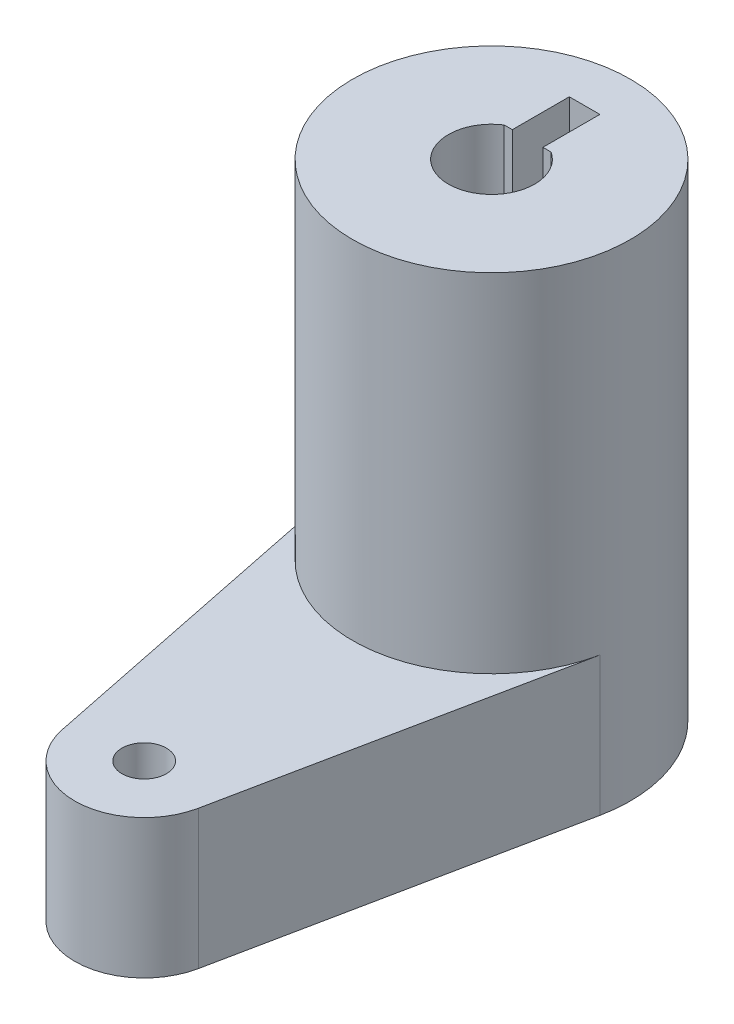
SolidWorks part; units mm, degrees
ref_plane "正面" through (0, 0, 0) normal (0, 0, 1) x (1, 0, 0)
ref_plane "平面" through (0, 0, 0) normal (0, 1, 0) x (1, 0, 0)
ref_plane "右側面" through (0, 0, 0) normal (1, 0, 0) x (0, 0, -1)
sketch "ｽｹｯﾁ1" plane through (0, 0, 0) normal (0, 1, 0) x (1, 0, 0)
  line L0 (-9.798, -2) -> (-4.899, -26)
  line L1 (4.899, -26) -> (9.798, -2)
  arc A0 (9.798, -2) -> (-9.798, -2) centre (0, 0) ccw
  arc A1 (-4.899, -26) -> (4.899, -26) centre (0, -25) ccw
  circle A2 centre (0, -25) radius 1.6
  dimension "D1" = 20
  dimension "D2" = 10
  dimension "D4" = 3.2
  dimension "D3" = 25
extrude "ﾎﾞｽ - 押し出し1" add sketch "ｽｹｯﾁ1" along normal blind 10
sketch "ｽｹｯﾁ3" plane through (0, 10, 0) normal (0, 1, 0) x (1, 0, 0)
  circle A0 centre (0, 0) radius 10
extrude "ﾎﾞｽ - 押し出し2" add sketch "ｽｹｯﾁ3" along normal blind 25
sketch "ｽｹｯﾁ2" plane through (0, 10, 0) normal (0, 1, 0) x (1, 0, 0)
  line L0 (-1.6882, 2.6) -> (-1.1, 2.6)
  line L7 (1.1, 2.6) -> (1.6882, 2.6)
  line L9 (-1.1, 2.6) -> (-1.1, 6.7)
  line L10 (-1.1, 6.7) -> (1.1, 6.7)
  line L11 (1.1, 2.6) -> (1.1, 6.7)
  line L12 (-1.1, 2.6) -> (1.1, 6.7) construction
  line L13 (-1.1, 6.7) -> (1.1, 2.6) construction
  arc A0 (-1.6882, 2.6) -> (1.6882, 2.6) centre (0, 0) ccw
  point P7 (0, 4.65)
  point P8 (0, 6.7)
  dimension "D1" = 2.6
  dimension "D2" = 6.2
  dimension "D3" = 2.2
  dimension "D4" = 4.1
extrude "ｶｯﾄ - 押し出し1" cut sketch "ｽｹｯﾁ2" against normal through all both and the other way through all
